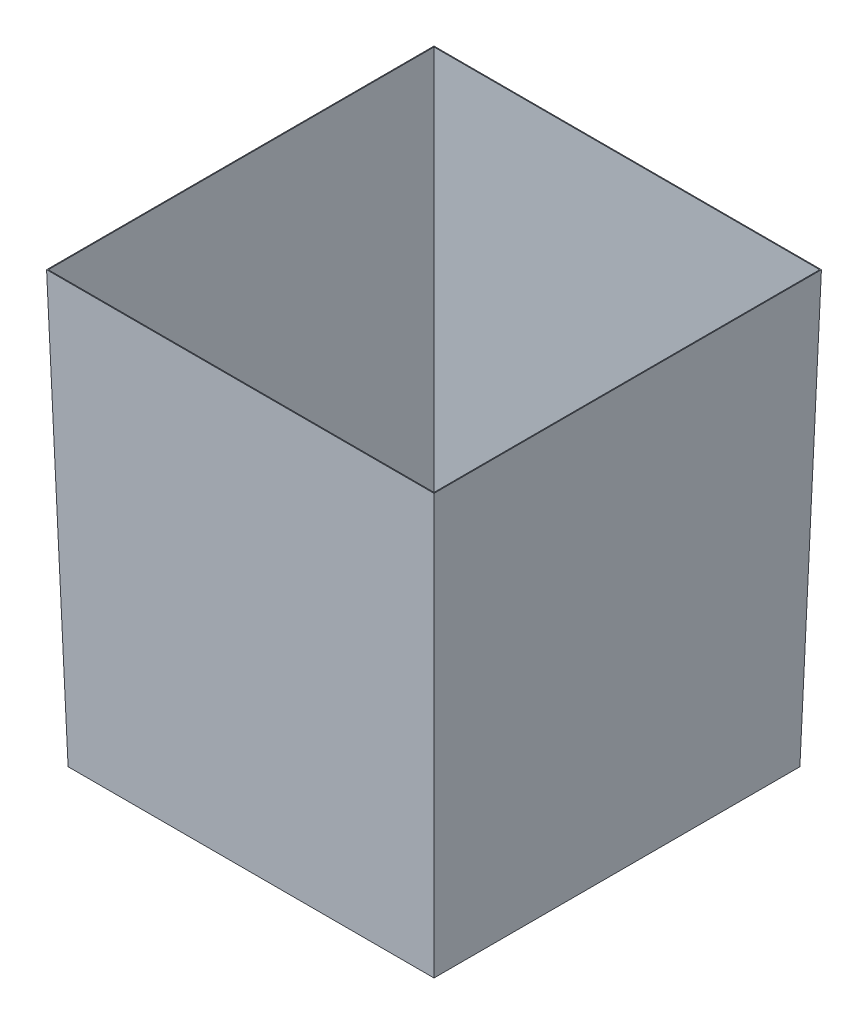
SolidWorks part; units mm, degrees
material "09Г2С ГОСТ 4543-71"
ref_plane "Спереди" through (0, 0, 0) normal (0, 0, 1) x (1, 0, 0)
ref_plane "Сверху" through (0, 0, 0) normal (0, 1, 0) x (1, 0, 0)
ref_plane "Справа" through (0, 0, 0) normal (1, 0, 0) x (0, 0, -1)
other "Configuration Table"
sketch "Эскиз1" plane through (0, 0, 0) normal (0, 1, 0) x (1, 0, 0)
  line L1 (-425, -425) -> (425, -425)
  line L2 (-425, -425) -> (-425, 425)
  line L3 (-425, 425) -> (425, 425)
  line L4 (425, -425) -> (425, 425)
ref_plane "Плоскость1" through (0, 1000, 0) normal (0, 1, 0) x (1, 0, 0)
sketch "Эскиз2" plane through (0, 1000, 0) normal (0, 1, 0) x (1, 0, 0)
  line L1 (-450, -450) -> (450, -450)
  line L2 (-450, -450) -> (-450, 450)
  line L3 (-450, 450) -> (450, 450)
  line L4 (450, -450) -> (450, 450)
loft "Корпус 850-900, H1000" add profiles "Эскиз1", "Эскиз2"
shell "Стенка и дно 2 мм" thickness 2 removed face at (0, 1000, 0)
